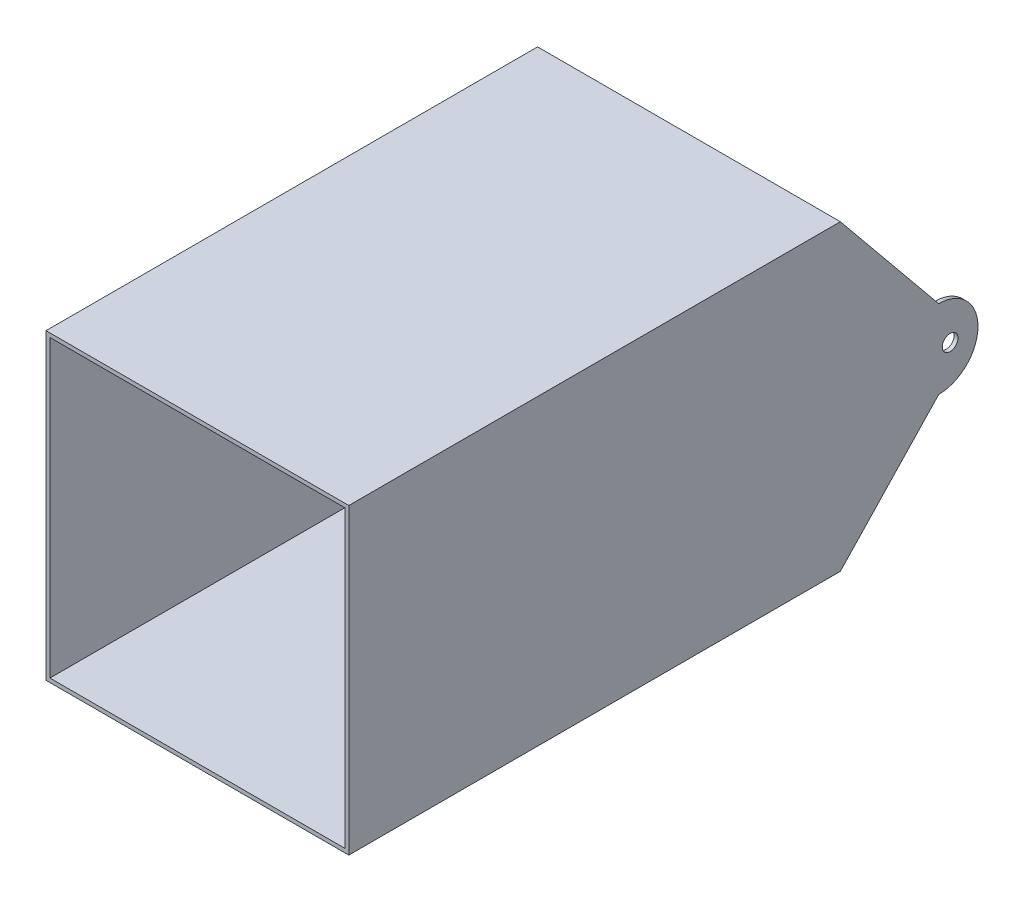
SolidWorks part; units mm, degrees
material "Cast Alloy Steel"
ref_plane "Front Plane" through (0, 0, 0) normal (0, 0, 1) x (1, 0, 0)
ref_plane "Top Plane" through (0, 0, 0) normal (0, 1, 0) x (1, 0, 0)
ref_plane "Right Plane" through (0, 0, 0) normal (1, 0, 0) x (0, 0, -1)
sketch "Sketch1" plane through (0, 0, 0) normal (0, 0, 1) x (1, 0, 0)
  line L0 (-77, 77) -> (77, 77)
  line L1 (-75, 75) -> (75, 75)
  line L2 (-75, 75) -> (-75, -75)
  line L3 (-75, -75) -> (75, -75)
  line L4 (75, 75) -> (75, -75)
  line L5 (-75, 75) -> (75, -75) construction
  line L6 (-75, -75) -> (75, 75) construction
  line L7 (77, 77) -> (77, -77)
  line L8 (-77, -77) -> (77, -77)
  line L9 (-77, 77) -> (-77, -77)
  point P0 (0, 0)
  dimension "D1" = 150
  dimension "D2" = 2
extrude "Boss-Extrude1" add sketch "Sketch1" along normal blind 250
sketch "Sketch2" plane through (0, 0, 0) normal (0, 0, -1) x (-1, 0, 0)
  line L1 (-77, 77) -> (77, 77)
  line L2 (-77, 77) -> (-77, -77)
  line L3 (-77, -77) -> (77, -77)
  line L4 (77, 77) -> (77, -77)
  line L5 (-75, 75) -> (75, 75)
  line L6 (-75, 75) -> (-75, -75)
  line L7 (-75, -75) -> (75, -75)
  line L8 (75, 75) -> (75, -75)
ref_plane "Plane1" through (0, 0, -50) normal (0, 0, 1) x (1, 0, 0)
sketch "Sketch3" plane through (0, 0, -50) normal (0, 0, 1) x (1, 0, 0)
  line L0 (-77, 77) -> (-77, -77) construction
  line L1 (-77, 15.8873) -> (77, 15.8873)
  line L2 (-77, 15.8873) -> (-77, -24.1127)
  line L3 (-77, -24.1127) -> (77, -24.1127)
  line L4 (77, 15.8873) -> (77, -24.1127)
  line L5 (77, 77) -> (77, -77) construction
  line L6 (-77, -4.1127) -> (77, -4.1127) construction
  line L7 (-75, 13.8873) -> (-75, -22.1127)
  line L8 (-75, -22.1127) -> (75, -22.1127)
  line L9 (75, 13.8873) -> (75, -22.1127)
  line L10 (-75, 13.8873) -> (75, 13.8873)
  dimension "D1" = 20
  dimension "D2" = 2
loft "Loft1" add section "Sketch3" section "Sketch2" connector at (-77, 15.8873, -50) connector at (-77, 77, 0)
loft "Cut-Loft1" cut section "Sketch3<3>" section "Sketch1<2>" connector at (75, 13.8873, -50) connector at (75, 75, 0)
sketch "Sketch3<3>" plane through (0, 0, -50) normal (0, 0, 1) x (1, 0, 0) same geometry as "Sketch3"
sketch "Sketch1<2>" plane through (0, 0, 0) normal (0, 0, 1) x (1, 0, 0) same geometry as "Sketch1"
sketch "Sketch7" plane through (77, 0, 0) normal (1, 0, 0) x (0, 0, -1)
  line L0 (50, 15.8873) -> (50, -24.1127) construction
  line L6 (50, 15.8873) -> (50, -24.1127)
  arc A3 (50, -24.1127) -> (50, 15.8873) centre (50, -4.1127) ccw
extrude "Boss-Extrude6" add sketch "Sketch7" against normal blind 2
extrude "Boss-Extrude7" add sketch "Sketch7<2>" along normal blind 2 from surface starting at face at (-77, 1.277, 58.3333)
sketch "Sketch7<2>" plane through (77, 0, 0) normal (1, 0, 0) x (0, 0, -1) same geometry as "Sketch7"
sketch "Sketch8" plane through (77, 0, 0) normal (1, 0, 0) x (0, 0, -1)
  line L0 (55.8344, -4.1127) -> (86.8563, -4.1127) construction
  circle A1 centre (55.8344, -4.1127) radius 4
  dimension "D1" = 8
extrude "Cut-Extrude1" cut sketch "Sketch8" against normal through all both and the other way through all
